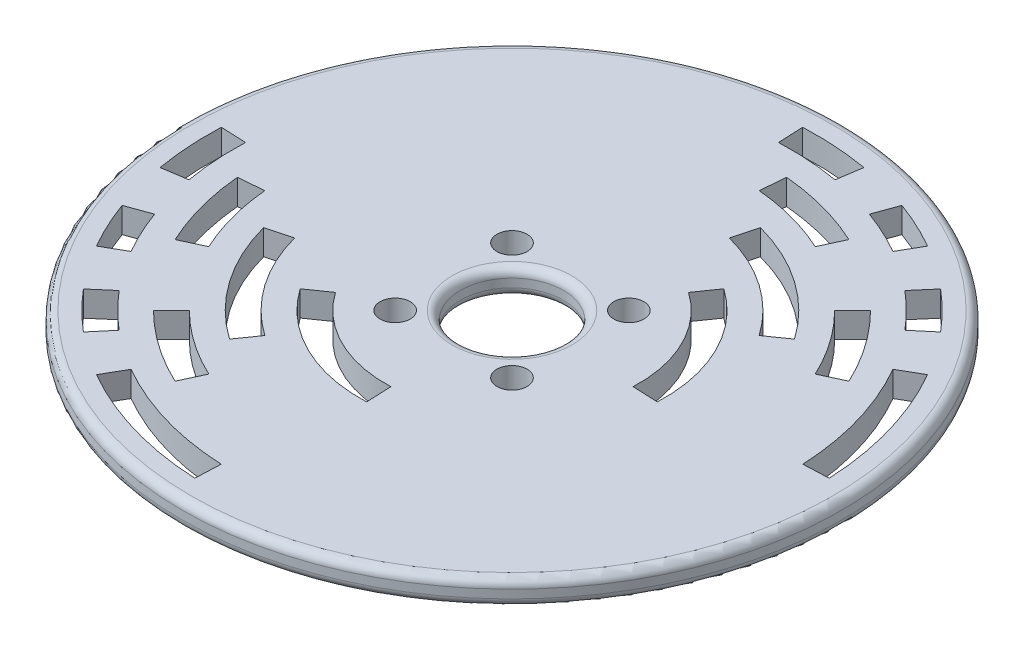
SolidWorks part; units mm, degrees
ref_plane "Front Plane" through (0, 0, 0) normal (0, 0, 1) x (1, 0, 0)
ref_plane "Top Plane" through (0, 0, 0) normal (0, 1, 0) x (1, 0, 0)
ref_plane "Right Plane" through (0, 0, 0) normal (1, 0, 0) x (0, 0, -1)
sketch "Sketch1" plane through (0, 0, 0) normal (0, 1, 0) x (1, 0, 0)
  line L0 (0, 0) -> (8.1776, 8.1776) construction
  circle A0 centre (0, 0) radius 6.096
  circle A1 centre (6.9148, 6.9148) radius 1.7859
  circle A2 centre (6.9148, -6.9148) radius 1.7859
  circle A3 centre (-6.9148, -6.9148) radius 1.7859
  circle A4 centre (-6.9148, 6.9148) radius 1.7859
  point P18 (0, 0)
  dimension "D2" = 3.5719
  dimension "D3" = 4
sketch "Sketch3" plane through (0, 0, 0) normal (0, 1, 0) x (1, 0, 0)
  line L1 (-1.4394, 32.9686) -> (-1.5703, 35.9657) construction
  line L2 (-24.4703, -11.4107) -> (-27.1892, -12.6785) construction
  line L3 (-20.2844, -5.4352) -> (-23.1822, -6.2117) construction
  line L4 (-12.0451, -17.2022) -> (-13.7658, -19.6596) construction
  line L5 (-19.0919, -19.0919) -> (-21.2132, -21.2132) construction
  line L6 (-26.8973, -2.3532) -> (-29.8858, -2.6147) construction
  line L7 (-11.4107, -24.4703) -> (-12.6785, -27.1892) construction
  line L8 (8.6036, 12.2873) -> (10.3244, 14.7447) construction
  line L9 (-1.4394, -32.9686) -> (-1.5703, -35.9657) construction
  line L10 (-16.5, -28.5788) -> (-18, -31.1769) construction
  line L11 (-21.212, -25.2795) -> (-23.1404, -27.5776) construction
  line L12 (-23.3345, -23.3345) -> (-25.4558, -25.4558) construction
  line L13 (-28.5788, -16.5) -> (-31.1769, -18) construction
  line L14 (-31.0099, -11.2867) -> (-33.8289, -12.3127) construction
  line L15 (32.9686, 1.4394) -> (35.9657, 1.5703)
  line L16 (0.6543, -14.9857) -> (0.7851, -17.9829) construction
  line L17 (-1.5703, 35.9657) -> (-1.4394, 32.9686)
  line L18 (6.1868, 35.4644) -> (5.7304, 32.4987)
  line L19 (12.3127, 33.8289) -> (11.2867, 31.0099)
  line L20 (18, 31.1769) -> (16.5, 28.5788)
  line L21 (-12.2873, -8.6036) -> (-14.7447, -10.3244) construction
  line L22 (-32.9686, 1.4394) -> (-35.9657, 1.5703) construction
  line L23 (14.9857, -0.6543) -> (17.9829, -0.7851) construction
  line L24 (23.1635, 27.5582) -> (21.212, 25.2795)
  line L25 (27.5776, 23.1404) -> (25.2795, 21.212)
  line L26 (31.1769, 18) -> (28.5788, 16.5)
  line L27 (-13.7658, -19.6596) -> (-12.0451, -17.2022)
  line L28 (14.9857, -0.6543) -> (17.9829, -0.7851)
  line L29 (11.2867, 31.0099) -> (12.3127, 33.8289) construction
  line L30 (10.3244, 14.7447) -> (8.6036, 12.2873)
  line L31 (-23.1822, -6.2117) -> (-20.2844, -5.4352)
  line L32 (16.5, 28.5788) -> (18, 31.1769) construction
  line L33 (-12.6785, -27.1892) -> (-11.4107, -24.4703)
  line L34 (23.3345, 23.3345) -> (25.4558, 25.4558) construction
  line L35 (25.2795, 21.212) -> (27.5776, 23.1404) construction
  line L36 (28.5788, 16.5) -> (31.1769, 18) construction
  line L37 (32.9686, 1.4394) -> (35.9657, 1.5703) construction
  line L38 (2.6147, 29.8858) -> (2.3532, 26.8973)
  line L39 (12.6785, 27.1892) -> (11.4107, 24.4703)
  line L40 (21.2132, 21.2132) -> (19.0919, 19.0919)
  line L41 (27.1892, 12.6785) -> (24.4703, 11.4107)
  line L42 (24.4703, 11.4107) -> (27.1892, 12.6785) construction
  line L43 (2.3532, 26.8973) -> (2.6147, 29.8858) construction
  line L44 (6.2117, 23.1822) -> (5.4352, 20.2844)
  line L45 (19.6596, 13.7658) -> (17.2022, 12.0451)
  line L46 (19.0919, 19.0919) -> (21.2132, 21.2132) construction
  line L47 (17.2022, 12.0451) -> (19.6596, 13.7658) construction
  line L48 (5.4352, 20.2844) -> (6.2117, 23.1822) construction
  line L49 (11.4107, 24.4703) -> (12.6785, 27.1892) construction
  line L50 (-21.2132, -21.2132) -> (-19.0919, -19.0919)
  line L51 (-27.1892, -12.6785) -> (-24.4703, -11.4107)
  line L52 (-29.8858, -2.6147) -> (-26.8973, -2.3532)
  line L53 (-14.7447, -10.3244) -> (-12.2873, -8.6036)
  line L54 (0.6543, -14.9857) -> (0.7851, -17.9829)
  line L55 (-18, -31.1769) -> (-16.5, -28.5788)
  line L56 (-23.1404, -27.5776) -> (-21.212, -25.2795)
  line L57 (-27.5582, -23.1635) -> (-25.2795, -21.212)
  line L58 (-31.1769, -18) -> (-28.5788, -16.5)
  line L59 (-33.8289, -12.3127) -> (-31.0099, -11.2867)
  line L60 (-35.4644, -6.1868) -> (-32.4987, -5.7304)
  line L61 (-35.9657, 1.5703) -> (-32.9686, 1.4394)
  line L62 (-1.4394, -32.9686) -> (-1.5703, -35.9657)
  arc A0 (14.9857, -0.6543) -> (8.6036, 12.2873) centre (0, 0) ccw
  arc A1 (17.9829, -0.7851) -> (10.3244, 14.7447) centre (0, 0) ccw
  arc A2 (-27.1892, -12.6785) -> (-29.8858, -2.6147) centre (0, 0) cw
  arc A3 (-24.4703, -11.4107) -> (-26.8973, -2.3532) centre (0, 0) cw
  arc A4 (24.4703, 11.4107) -> (19.0919, 19.0919) centre (0, 0) ccw
  arc A5 (27.1892, 12.6785) -> (21.2132, 21.2132) centre (0, 0) ccw
  arc A6 (32.9686, 1.4394) -> (28.5788, 16.5) centre (0, 0) ccw
  arc A7 (35.9657, 1.5703) -> (31.1769, 18) centre (0, 0) ccw
  arc A8 (25.2795, 21.212) -> (21.212, 25.2795) centre (0, 0) ccw
  arc A9 (27.5776, 23.1404) -> (23.1635, 27.5582) centre (0, 0) ccw
  arc A10 (18, 31.1769) -> (12.3127, 33.8289) centre (0, 0) ccw
  arc A11 (16.5, 28.5788) -> (11.2867, 31.0099) centre (0, 0) ccw
  arc A12 (6.1868, 35.4644) -> (-1.5703, 35.9657) centre (0, 0) ccw
  arc A13 (5.7304, 32.4987) -> (-1.4394, 32.9686) centre (0, 0) ccw
  arc A14 (17.2022, 12.0451) -> (5.4352, 20.2844) centre (0, 0) ccw
  arc A15 (19.6596, 13.7658) -> (6.2117, 23.1822) centre (0, 0) ccw
  arc A16 (11.4107, 24.4703) -> (2.3532, 26.8973) centre (0, 0) ccw
  arc A17 (12.6785, 27.1892) -> (2.6147, 29.8858) centre (0, 0) ccw
  arc A18 (-13.7658, -19.6596) -> (-23.1822, -6.2117) centre (0, 0) cw
  arc A19 (-12.0451, -17.2022) -> (-20.2844, -5.4352) centre (0, 0) cw
  arc A20 (-32.4987, -5.7304) -> (-32.9686, 1.4394) centre (0, 0) cw
  arc A21 (-35.4644, -6.1868) -> (-35.9657, 1.5703) centre (0, 0) cw
  arc A22 (-28.5788, -16.5) -> (-31.0099, -11.2867) centre (0, 0) cw
  arc A23 (-31.1769, -18) -> (-33.8289, -12.3127) centre (0, 0) cw
  arc A24 (-23.1404, -27.5776) -> (-27.5582, -23.1635) centre (0, 0) cw
  arc A25 (-21.212, -25.2795) -> (-25.2795, -21.212) centre (0, 0) cw
  arc A26 (-1.5703, -35.9657) -> (-18, -31.1769) centre (0, 0) cw
  arc A27 (-1.4394, -32.9686) -> (-16.5, -28.5788) centre (0, 0) cw
  arc A28 (-12.6785, -27.1892) -> (-21.2132, -21.2132) centre (0, 0) cw
  arc A29 (-11.4107, -24.4703) -> (-19.0919, -19.0919) centre (0, 0) cw
  arc A30 (0.7851, -17.9829) -> (-14.7447, -10.3244) centre (0, 0) cw
  arc A31 (0.6543, -14.9857) -> (-12.2873, -8.6036) centre (0, 0) cw
  point P4 (0, 0)
  point P14 (0, 0)
  point P16 (0, 0)
  point P19 (0, 0)
  point P27 (0, 0)
  point P29 (0, 0)
  point P32 (0, 0)
  point P33 (0, 0)
  point P51 (0, 0)
  point P57 (0, 0)
sketch "Sketch4" plane through (0, 0, 0) normal (0, 1, 0) x (1, 0, 0)
  circle A0 centre (0, 0) radius 39
extrude "Boss-Extrude1" add sketch "Sketch4" along normal blind 3
extrude "Cut-Extrude1" cut sketch "Sketch3" along normal blind 3
extrude "Cut-Extrude3" cut sketch "Sketch1" along normal blind 3
fillet "Fillet1" radius 1 4 edges at (0, 0, 6.096) (0, 3, 6.096) (0, 3, 39) (0, 0, 39)
